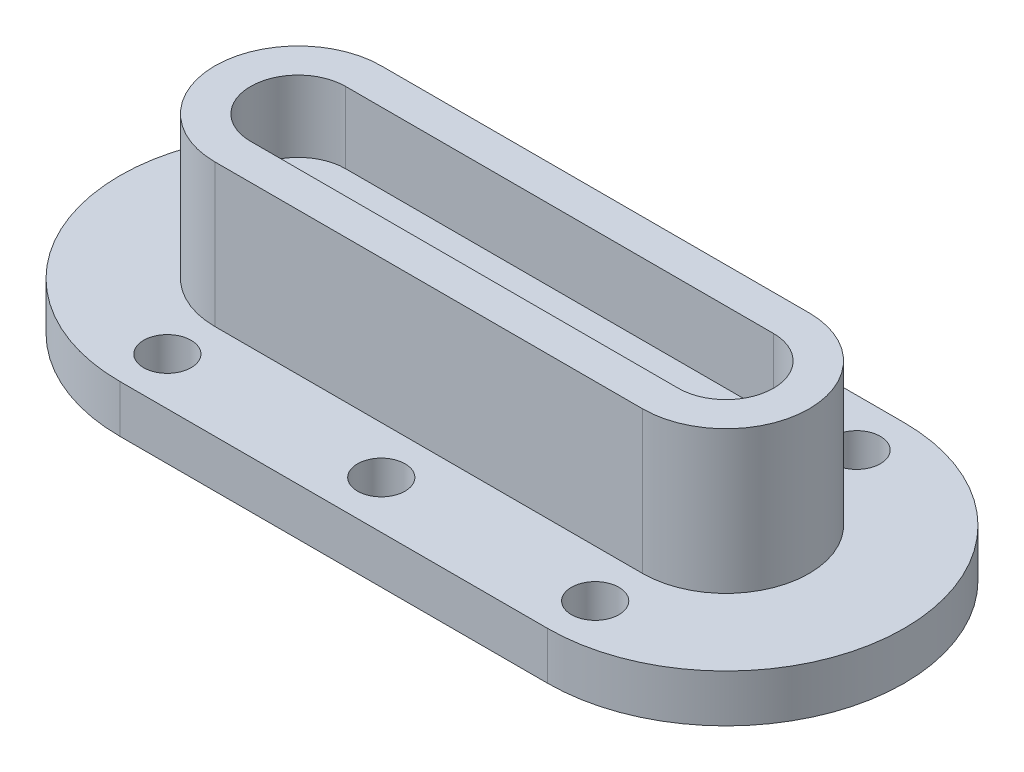
SolidWorks part; units mm, degrees
ref_plane "Front Plane" through (0, 0, 0) normal (0, 0, 1) x (1, 0, 0)
ref_plane "Top Plane" through (0, 0, 0) normal (0, 1, 0) x (1, 0, 0)
ref_plane "Right Plane" through (0, 0, 0) normal (1, 0, 0) x (0, 0, -1)
sketch "Sketch1" plane through (0, 0, 0) normal (0, 1, 0) x (1, 0, 0)
  line L0 (90, 0) -> (-90, 0) construction
  line L1 (90, -75) -> (-90, -75)
  line L2 (90, 75) -> (-90, 75)
  line L3 (90, 0) -> (-90, 0) construction
  line L4 (90, -35) -> (-90, -35)
  line L5 (90, 35) -> (-90, 35)
  line L6 (90, 0) -> (-90, 0) construction
  line L7 (90, -20) -> (-90, -20)
  line L8 (90, 20) -> (-90, 20)
  line L9 (90, 0) -> (-90, 0) construction
  line L10 (90, -55) -> (-90, -55) construction
  line L11 (90, 55) -> (-90, 55) construction
  arc A0 (90, -75) -> (90, 75) centre (90, 0) ccw
  arc A1 (-90, 75) -> (-90, -75) centre (-90, 0) ccw
  arc A2 (90, -35) -> (90, 35) centre (90, 0) ccw
  arc A3 (-90, 35) -> (-90, -35) centre (-90, 0) ccw
  arc A4 (90, -20) -> (90, 20) centre (90, 0) ccw
  arc A5 (-90, 20) -> (-90, -20) centre (-90, 0) ccw
  arc A6 (90, -55) -> (90, 55) centre (90, 0) ccw construction
  arc A7 (-90, 55) -> (-90, -55) centre (-90, 0) ccw construction
  circle A8 centre (-90, 55) radius 10
  circle A9 centre (-90, -55) radius 10
  circle A10 centre (0, 55) radius 10
  circle A11 centre (0, -55) radius 10
  circle A12 centre (90, 55) radius 10
  circle A13 centre (90, -55) radius 10
  circle A14 centre (90, 0) radius 7.5
  circle A15 centre (0, 0) radius 7.5
  circle A16 centre (-90, 0) radius 7.5
  point P2 (0, 0)
  point P10 (0, 0)
  point P16 (0, 0)
  point P23 (0, 0)
  dimension "D1" = 75
  dimension "D3" = 35
  dimension "D4" = 20
  dimension "D6" = 20
  dimension "D8" = 90
  dimension "D9" = 15
  dimension "D11" = 90
  dimension "D2" = 180
  dimension "D5" = 110
  dimension "D7" = 3
  dimension "D10" = 3
extrude "Boss-Extrude1" add sketch "Sketch1" along normal blind 20 contours L2 A1 L1 A0 A13 A12 A11 A10 A9 A8 A3 L5 A2 L4 | L5 A3 L4 A2 A5 L8 A4 L7 | L8 A5 L7 A4 A16 A15 A14 region at (0, 0, 71.3751) region at (0, 0, 32.4038) region at (0, 0, 17.7639)
extrude "Boss-Extrude2" add sketch "Sketch1<4>" along normal blind 50 contours L8 A5 L7 A4 A16 A15 A14 region at (0, 0, 17.7639)
sketch "Sketch1<4>" plane through (0, 0, 0) normal (0, 1, 0) x (1, 0, 0) same geometry as "Sketch1"
extrude "Boss-Extrude3" add sketch "Sketch1<5>" along normal blind 80 contours L5 A3 L4 A2 A5 L8 A4 L7 region at (0, 0, 32.4038)
sketch "Sketch1<5>" plane through (0, 0, 0) normal (0, 1, 0) x (1, 0, 0) same geometry as "Sketch1"
